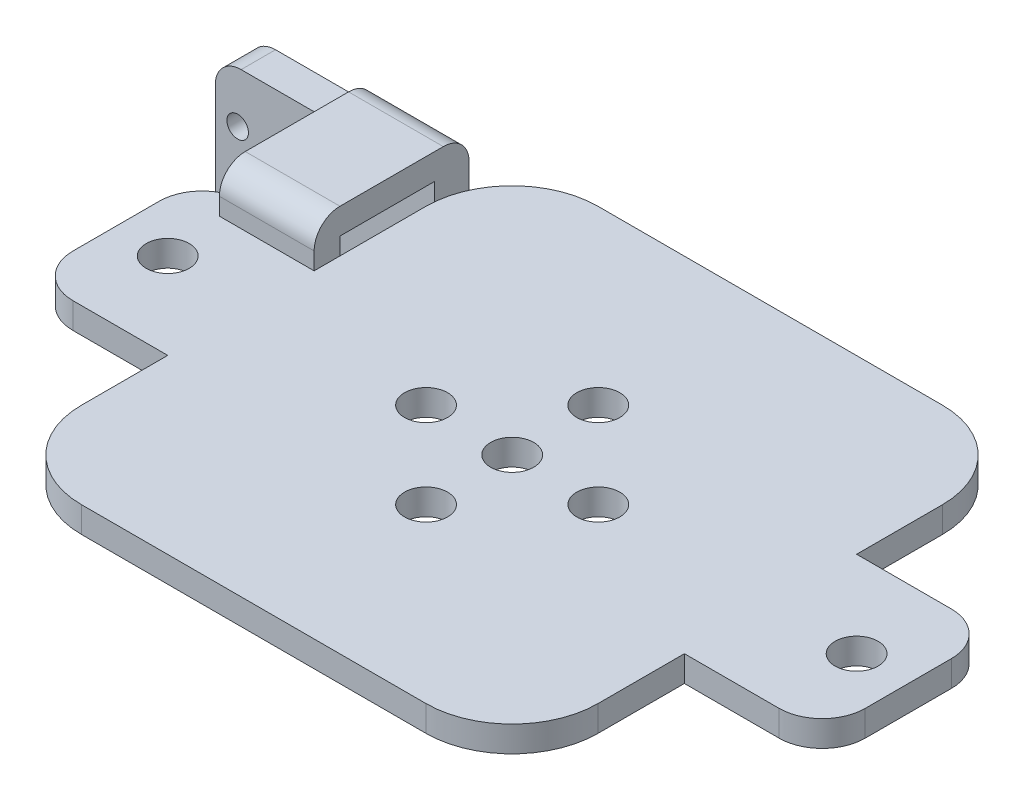
SolidWorks part; units mm, degrees
ref_plane "Front Plane" through (0, 0, 0) normal (0, 0, 1) x (1, 0, 0)
ref_plane "Top Plane" through (0, 0, 0) normal (0, 1, 0) x (1, 0, 0)
ref_plane "Right Plane" through (0, 0, 0) normal (1, 0, 0) x (0, 0, -1)
sketch "Sketch1" plane through (0, 0, 0) normal (0, 1, 0) x (1, 0, 0)
  line L0 (69.4221, 30.0207) -> (-16.2022, 30.0207) construction
  line L1 (0, 0) -> (60, 0)
  line L2 (0, 0) -> (0, 60)
  line L3 (0, 60) -> (60, 60)
  line L4 (60, 0) -> (60, 60)
  line L5 (30, 63.9004) -> (30, -4.8431) construction
  line L6 (23.4653, 40.0207) -> (37.3207, 40.0207) construction
  line L7 (20, 36.8255) -> (20, 23.5223) construction
  line L8 (23.8167, 20.0207) -> (36.7183, 20.0207) construction
  line L9 (40, 25.4802) -> (40, 39.2352) construction
  line L10 (64.811, 30) -> (-8.1915, 30) construction
  circle A0 centre (30, 40.0207) radius 2.5
  circle A1 centre (20, 30.0207) radius 2.5
  circle A2 centre (30, 20.0207) radius 2.5
  circle A3 centre (40, 30.0207) radius 2.5
  circle A4 centre (30, 30.0207) radius 2.5
  dimension "D3" = 5
  dimension "D4" = 5
  dimension "D5" = 5
  dimension "D6" = 5
  dimension "D11" = 5
  dimension "D1" = 60
  dimension "D2" = 60
  dimension "D7" = 10
  dimension "D8" = 10
  dimension "D9" = 10
  dimension "D10" = 10
extrude "Boss-Extrude2" add sketch "Sketch1" along normal blind 5
sketch "Sketch3" plane through (0, 0, 0) normal (0, 1, 0) x (1, 0, 0)
  line L0 (73.9499, 30) -> (-18.7239, 30) construction
  line L1 (30, 64.8678) -> (30, -8.394) construction
  line L2 (32.5, 40.0207) -> (75.2565, 40.0207) construction
  line L3 (75.2565, 40.0207) -> (-19.5638, 40.0207) construction
  line L4 (-35, 20.0207) -> (81.6027, 20.0207) construction
  line L5 (60, 0) -> (60, 60) construction
  line L6 (60, 40.0207) -> (95, 40.0207)
  line L7 (60, 40.0207) -> (60, 20.0207)
  line L8 (60, 20.0207) -> (95, 20.0207)
  line L9 (95, 40.0207) -> (95, 20.0207)
  line L10 (0, 60) -> (0, 0) construction
  line L11 (0, 20.0207) -> (-35, 20.0207)
  line L12 (0, 20.0207) -> (0, 40.0207)
  line L13 (0, 40.0207) -> (-35, 40.0207)
  line L14 (-35, 20.0207) -> (-35, 40.0207)
  circle A0 centre (30, 40.0207) radius 2.5 construction
  dimension "D1" = 35
  dimension "D2" = 35
extrude "Boss-Extrude3" add sketch "Sketch3" along normal blind 5
sketch "Sketch5" plane through (0, 0, 0) normal (0, 1, 0) x (1, 0, 0)
  line L0 (42.5, 30.0207) -> (107.6368, 30.0207) construction
  line L1 (107.6368, 30.0207) -> (-59.7355, 30.0207) construction
  line L2 (60, 40.5295) -> (60, 5.0875) construction
  line L3 (60, 40.0207) -> (60, 60) construction
  line L4 (60, 0) -> (60, 20.0207) construction
  line L5 (0, 40.0207) -> (0, 13.7818) construction
  line L6 (0, 20.0207) -> (0, 0) construction
  circle A0 centre (40, 30.0207) radius 2.5 construction
  circle A1 centre (70, 30.0207) radius 2.5
  circle A2 centre (-10, 30.0207) radius 2.5
  dimension "D2" = 10
  dimension "D3" = 5
  dimension "D4" = 5
  dimension "D1" = 10
extrude "Cut-Extrude1" cut sketch "Sketch5" along normal through all
fillet "Fillet1" radius 10 2 edges at (95, 2.5, -20.0207) (95, 2.5, -40.0207)
fillet "Fillet2" radius 10 2 edges at (-35, 2.5, -20.0207) (-35, 2.5, -40.0207)
fillet "Fillet3" radius 10 4 edges at (60, 2.5, 0) (0, 2.5, 0) (60, 2.5, -60) (0, 2.5, -60)
sketch "Sketch6" plane through (0, 0, -60) normal (0, 0, -1) x (-1, 0, 0)
  line L0 (35, 5) -> (35, 0) construction
  line L1 (-95, 5) -> (35, 5)
  line L2 (-95, 5) -> (-95, 3)
  line L3 (-95, 3) -> (35, 3)
  line L4 (35, 5) -> (35, 3)
extrude "Cut-Extrude2" cut sketch "Sketch6" against normal through all both and the other way through all
sketch "Sketch7" plane through (0, 3, 0) normal (0, 1, 0) x (1, 0, 0)
  line L0 (-16, 40.0207) -> (-16, 42.3391)
  line L1 (-25, 40.0207) -> (0, 40.0207) construction
  line L2 (-16, 40.0207) -> (-16, 20.0207)
  line L3 (0, 20.0207) -> (-25, 20.0207) construction
  line L4 (-16, 20.0207) -> (-38.9232, 20.0207)
  line L5 (-38.9232, 20.0207) -> (-38.9232, 39.7252)
  line L6 (-14.1693, 39.7252) -> (-214.1693, 39.7252) construction
  line L8 (-16, 42.3391) -> (-38.9232, 42.3391)
  line L9 (-38.9232, 42.3391) -> (-38.9232, 39.7252)
  line L11 (98.9232, 20.0207) -> (98.9232, 39.7252)
  line L12 (76, 20.0207) -> (98.9232, 20.0207)
  line L13 (76, 40.0207) -> (76, 20.0207)
  line L14 (76, 40.0207) -> (76, 44.0066)
  line L15 (76, 44.0066) -> (98.9232, 44.0066)
  line L16 (98.9232, 44.0066) -> (98.9232, 39.7252)
extrude "Cut-Extrude4" cut sketch "Sketch7" against normal through all both and the other way through all
fillet "Fillet4" radius 5 4 edges at (-16, 1.5, -20.0207) (-16, 1.5, -40.0207) (76, 1.5, -20.0207) (76, 1.5, -40.0207)
sketch "Sketch8" plane through (0, 0, -40.0207) normal (0, 0, -1) x (-1, 0, 0)
  line L1 (0, 3) -> (11, 3)
  line L2 (0, 3) -> (0, 8)
  line L3 (0, 8) -> (11, 8)
  line L4 (11, 3) -> (11, 8)
extrude "Boss-Extrude4" add sketch "Sketch8" against normal blind 3
sketch "Sketch9" plane through (0, 0, -40.0207) normal (0, 0, -1) x (-1, 0, 0)
  line L1 (0, 8) -> (11, 8)
  line L2 (0, 8) -> (0, 5)
  line L3 (0, 5) -> (11, 5)
  line L4 (11, 8) -> (11, 5)
extrude "Boss-Extrude5" add sketch "Sketch9" along normal blind 15
sketch "Sketch10" plane through (0, 5, 0) normal (0, -1, 0) x (1, 0, 0)
  line L1 (-25.4802, -51.0235) -> (-25.4802, -55.0207)
  line L2 (-25.4802, -55.0207) -> (-11, -55.0207)
  line L3 (-11, -55.0207) -> (0, -55.0207)
  line L5 (0, -55.0207) -> (0, -51.0235)
  line L6 (-25.4802, -51.0235) -> (0, -51.0235)
  line L7 (0, -55.0207) -> (0, -40.0207) construction
extrude "Boss-Extrude6" add sketch "Sketch10" along normal blind 21
sketch "Sketch11" plane through (0, 0, -51.0235) normal (0, 0, 1) x (1, 0, 0)
  circle A0 centre (-22.8802, -0.9317) radius 1.25
  circle A1 centre (-22.8802, -10.4317) radius 1.25
extrude "Cut-Extrude5" cut sketch "Sketch11" against normal blind 10 and the other way through all
fillet "Fillet5" radius 3 5 edges at (-5.5, 8, -37.0207) (-5.5, 8, -55.0207) (0, -16, -53.0221) (-25.4802, 5, -53.0221) (-25.4802, -16, -53.0221)
